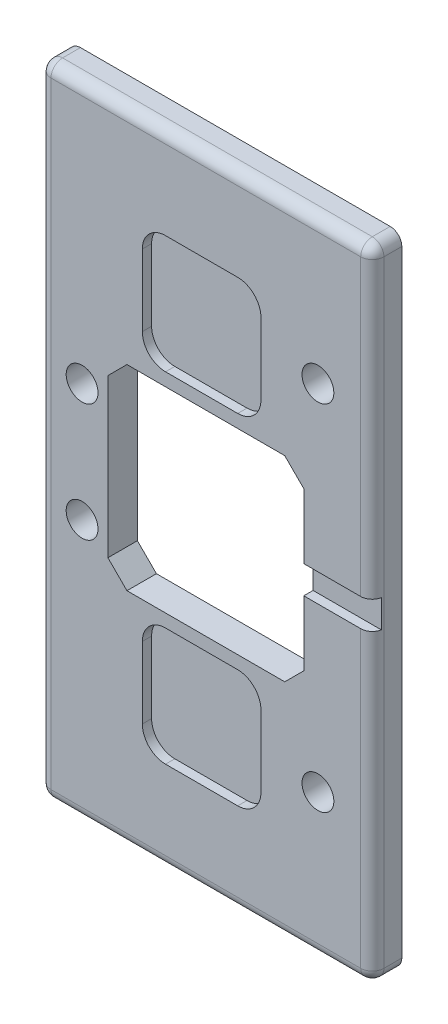
SolidWorks part; units mm, degrees
ref_plane "Front Plane" through (0, 0, 0) normal (0, 0, 1) x (1, 0, 0)
ref_plane "Top Plane" through (0, 0, 0) normal (0, 1, 0) x (1, 0, 0)
ref_plane "Right Plane" through (0, 0, 0) normal (1, 0, 0) x (0, 0, -1)
sketch "Sketch1" plane through (0, 0, 0) normal (0, 0, 1) x (1, 0, 0)
  line L0 (68.0566, 68.87) -> (126.0194, 68.87)
  line L22 (62.2146, 68.87) -> (68.0566, 68.87)
  line L28 (62.2146, -68.87) -> (126.0194, -68.87)
  line L31 (126.0194, -68.87) -> (126.0194, 68.87)
  line L38 (62.2146, 68.87) -> (54.2999, 68.87)
  line L40 (62.2146, -68.87) -> (54.2999, -68.87)
  line L41 (54.2999, 68.87) -> (54.2999, -68.87)
extrude "Boss-Extrude3" add sketch "Sketch1" along normal blind 6.35 contours L22 region at (90.1597, 0, 0)
ref_plane "Plane1" through (0, 0, 0) normal (0, -1, 0) x (-1, 0, 0)
sketch "Sketch6" plane through (0, 0, 0) normal (0, 0, -1) x (-1, 0, 0)
  circle A16 centre (-63.5, 12.7) radius 3.429
  circle A17 centre (-114.3, 38.1) radius 3.429
  circle A18 centre (-114.3, -38.1) radius 3.429
  circle A19 centre (-63.5, -12.7) radius 3.429
  point P0 (-63.5, -12.7)
  dimension "D1" = 6.858
extrude "Cut-Extrude5" cut sketch "Sketch6" against normal up to surface (6.35 mm away) up to face at (90.1597, 0, 6.35)
fillet "Fillet2" radius 2.5 8 edges at (54.2999, 68.87, 3.175) (54.2999, -68.87, 3.175) (126.0194, -68.87, 3.175) (126.0194, 68.87, 3.175) (90.1597, 68.87, 6.35) (90.1597, -68.87, 6.35) (54.2999, 0, 6.35) (126.0194, 0, 6.35)
sketch "Sketch7" plane through (0, 0, 6.35) normal (0, 0, 1) x (1, 0, 0)
  line L0 (90.1597, -66.37) -> (90.1597, 66.37) construction
  line L3 (56.7999, -66.37) -> (123.5194, -66.37) construction
  line L5 (123.5194, 66.37) -> (56.7999, 66.37) construction
  line L6 (56.7999, 0) -> (123.5194, 0) construction
  line L7 (56.7999, 66.37) -> (56.7999, -66.37) construction
  line L8 (123.5194, -66.37) -> (123.5194, 66.37) construction
  circle A0 centre (90.1597, 0) radius 3.43
  dimension "D1" = 6.86
extrude "Cut-Extrude6" cut sketch "Sketch7" against normal through all
sketch "Sketch10" plane through (0, 0, 6.35) normal (0, 0, 1) x (1, 0, 0)
  line L14 (69.065, 21.0947) -> (111.2544, 21.0947)
  line L15 (69.065, 21.0947) -> (69.065, -21.0947)
  line L16 (69.065, -21.0947) -> (111.2544, -21.0947)
  line L17 (111.2544, 21.0947) -> (111.2544, -21.0947)
extrude "Cut-Extrude8" cut sketch "Sketch10" against normal through all
sketch "Sketch11" plane through (0, 0, 6.35) normal (0, 0, 1) x (1, 0, 0)
  line L0 (123.5194, -66.37) -> (123.5194, 66.37) construction
  line L1 (123.5194, -3) -> (111.2544, -3)
  line L3 (123.5194, 3) -> (111.2544, 3)
  line L4 (111.2544, -3) -> (111.2544, 3)
  line L5 (111.2544, -21.0947) -> (111.2544, 21.0947) construction
  line L6 (117.3869, 3) -> (117.3869, 66.37) construction
  line L7 (123.5194, -3) -> (127.3985, -3)
  line L9 (123.5194, 3) -> (127.3985, 3)
  line L10 (127.3985, -3) -> (127.3985, 3)
  line L11 (123.5194, 66.37) -> (56.7999, 66.37) construction
  line L12 (117.3869, -3) -> (117.3869, -66.37) construction
  line L13 (56.7999, -66.37) -> (123.5194, -66.37) construction
  dimension "D1" = 6
extrude "Cut-Extrude9" cut sketch "Sketch11" against normal blind 2
sketch "Sketch12" plane through (0, 0, 6.35) normal (0, 0, 1) x (1, 0, 0)
  line L0 (76.4742, -44.3) -> (76.4742, -50.9707) construction
  line L1 (81.4742, -49.3) -> (76.4742, -49.3) construction
  line L2 (96.8742, -23.9) -> (102.0243, -23.9) construction
  line L3 (102.0243, -23.9) -> (101.8742, -28.9) construction
  line L5 (76.4742, -49.3) -> (102.0243, -49.3)
  line L6 (76.4742, -49.3) -> (76.4742, -23.9)
  line L7 (76.4742, -23.9) -> (102.0243, -23.9)
  line L8 (102.0243, -49.3) -> (102.0243, -23.9)
extrude "Cut-Extrude10" cut sketch "Sketch12" against normal blind 2
fillet "Fillet3" radius 5 4 edges at (102.0243, -23.9, 5.35) (76.4742, -23.9, 5.35) (76.4742, -49.3, 5.35) (102.0243, -49.3, 5.35)
mirror "Mirror1" about plane through (0, 0, 0) normal (0, -1, 0) of "Fillet3", "Cut-Extrude10"
chamfer "Chamfer1" distance 4.1 angle 45 4 edges at (69.065, -21.0947, 3.175) (69.065, 21.0947, 3.175) (111.2544, 21.0947, 3.175) (111.2544, -21.0947, 3.175)
